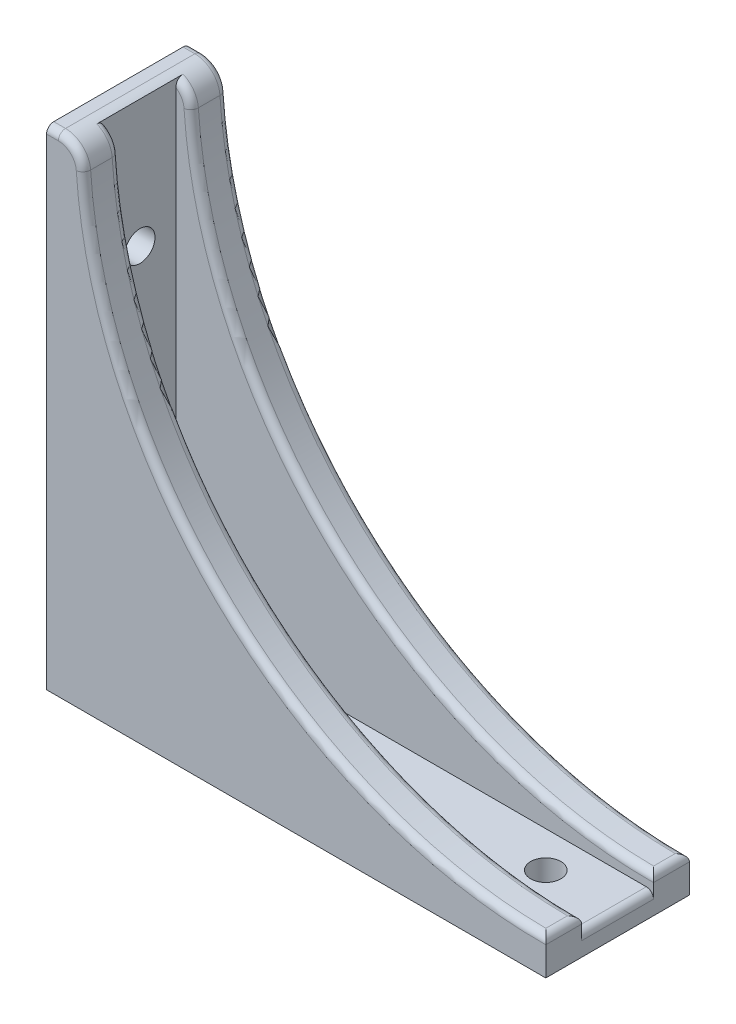
SolidWorks part; units mm, degrees
ref_plane "Front Plane" through (0, 0, 0) normal (0, 0, 1) x (1, 0, 0)
ref_plane "Top Plane" through (0, 0, 0) normal (0, 1, 0) x (1, 0, 0)
ref_plane "Right Plane" through (0, 0, 0) normal (1, 0, 0) x (0, 0, -1)
sketch "Sketch1" plane through (0, 0, 0) normal (0, 0, 1) x (1, 0, 0)
  line L0 (59.5, 5) -> (59.5, 0)
  line L1 (0, 0) -> (69.5, 0)
  line L2 (0, 0) -> (0, 68)
  line L3 (0, 68) -> (69.5, 68)
  line L4 (69.5, 0) -> (69.5, 68)
  line L5 (69.5, 68) -> (5, 68)
  line L6 (69.5, 68) -> (69.5, 5)
  line L7 (69.5, 5) -> (5, 5)
  line L8 (5, 68) -> (5, 5)
  line L9 (69.5, 68) -> (3, 68)
  line L10 (69.5, 68) -> (69.5, 3)
  line L11 (69.5, 3) -> (3, 3)
  line L12 (3, 68) -> (3, 3)
  dimension "D1" = 10
  dimension "D2" = 2
  dimension "D3" = 2
  dimension "D4" = 3
  dimension "D5" = 3
  dimension "D6" = 68
  dimension "D7" = 59.5
extrude "Boss-Extrude1" add sketch "Sketch1" along normal blind 20 contours L12 L3 L2 L1 L4 L11 | L3 L12 L11 L4 L7 L8 | L11 L4 L7 L0 | L4 L11 L0 L1 region at (64.5, 4, 0) region at (58.6388, 4, 0) region at (64.5, 1.5, 0) region at (58.5964, 1.5, 0)
extrude "Cut-Extrude1" cut sketch "Sketch1<3>" along normal offset from surface (15 mm away) 5 contours L3 L12 L11 L4 L7 L8 | L11 L4 L7 L0 region at (64.5, 4, 0) region at (58.6388, 4, 0) up to face at (24.8333, 24.3333, 20)
sketch "Sketch1<3>" plane through (0, 0, 0) normal (0, 0, 1) x (1, 0, 0) same geometry as "Sketch1"
extrude "Boss-Extrude2" add sketch "Sketch1<4>" along normal blind 5 contours L3 L12 L11 L4 L7 L8 | L11 L4 L7 L0 region at (64.5, 4, 0) region at (58.6388, 4, 0)
sketch "Sketch1<4>" plane through (0, 0, 0) normal (0, 0, 1) x (1, 0, 0) same geometry as "Sketch1"
sketch "Sketch2" plane through (0, 0, 0) normal (0, -1, 0) x (1, 0, 0)
  line L0 (3, 15) -> (3, 5) construction
  line L1 (0, 20) -> (0, 0) construction
  circle A0 centre (59.5, 10) radius 2.1
  point P5 (3, 10)
  dimension "D1" = 4.2
  dimension "D2" = 59.5
extrude "Cut-Extrude2" cut sketch "Sketch2" against normal up to next
sketch "Sketch3" plane through (0, 0, 0) normal (-1, 0, 0) x (0, 0, 1)
  line L0 (15, 3) -> (5, 3) construction
  line L2 (20, 0) -> (0, 0) construction
  circle A0 centre (10, 25) radius 2.1
  circle A1 centre (10, 50) radius 2.1
  point P7 (10, 3)
  point P9 (10, 0)
  dimension "D1" = 4.2
  dimension "D2" = 25
  dimension "D3" = 25
extrude "Cut-Extrude3" cut sketch "Sketch3" against normal up to next
fillet "Fillet2" radius 64 2 edges at (5, 5, 17.5) (5, 5, 2.5)
fillet "Fillet3" radius 3.5 2 edges at (3, 3, 10) (5, 68, 2.5)
fillet "Fillet4" radius 1 17 edges at (0.8212, 68, 0) (0.8212, 68, 20) (25.2719, 22.261, 0) (25.2719, 22.261, 20) (69.5, 3, 10) (25.2719, 22.261, 15) (25.2719, 22.261, 5) (69.2461, 5, 0) (69.2461, 5, 20) (69.2461, 5, 15) (69.2461, 5, 5) (4.0333, 67.056, 0) (4.0333, 67.056, 20) (4.4918, 66.5324, 15) (4.4918, 66.5324, 5) (69.5, 5, 2.5) (69.5, 5, 17.5)
